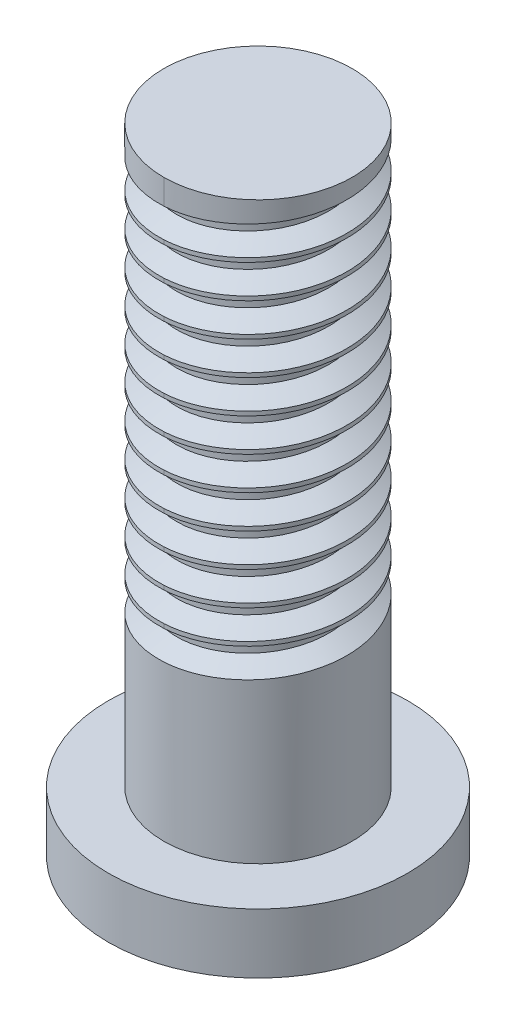
SolidWorks part; units mm, degrees
material "6061-T6 (SS)"
ref_plane "Front Plane" through (0, 0, 0) normal (1, 0, 0) x (0, 1, 0)
ref_plane "Top Plane" through (0, 0, 0) normal (0, 0, 1) x (0, 1, 0)
ref_plane "Right Plane" through (0, 0, 0) normal (0, 1, 0) x (-1, 0, 0)
sketch "Sketch1" plane through (0, 0, 0) normal (1, 0, 0) x (0, 1, 0)
  line L0 (0, 0) -> (-28.8256, 0)
  line L1 (-26.9494, 6.35) -> (-24.4094, 6.35)
  line L2 (-24.4094, 6.35) -> (-24.4094, 4)
  line L3 (-24.4094, 4) -> (0, 4)
  line L5 (0, 4) -> (0, 0)
  line L6 (-17.399, 0) -> (-17.399, 4) construction
  arc A0 (-28.8256, 0) -> (-26.9494, 6.35) centre (-17.1416, 0) cw
  point P7 (-28.4424, 6.35)
  point P11 (-21.0337, 4)
  point P12 (-0.2338, 4)
  point P13 (-17.399, 4)
  point P14 (-27.559, 4)
  dimension "D6" = 11.684
  dimension "D1" = 4
  dimension "D2" = 6.35
  dimension "D5" = 2.54
  dimension "D3" = 7.0104
  dimension "D4" = 17.399
revolve "Revolve1" add sketch "Sketch1" angle 360 about L0 region at (0, -8.6995, 2) region at (0, -23.4299, 2.426)
thread "Thread1" pitch 1.4111 method cut profile "Thread Profile1" start angle 0, offset 0, length 17.399, pitch 1.4111, diameter 8
ref_plane "Plane1" through (-4, 0, 0) normal (0, 0, 1) x (-1, 0, 0)
sketch "Thread Profile1" plane through (-4, 0, 0) normal (0, 0, 1) x (-1, 0, 0)
  line L0 (0, 0) -> (0, 1.4111) construction
  line L11 (0, 0) -> (0, 1.2347)
  line L12 (0, 1.2347) -> (-0.7638, 0.7937)
  line L13 (-0.7638, 0.7937) -> (-0.7638, 0.441)
  line L15 (-0.7638, 0.441) -> (0, 0)
  line L17 (-0.7638, 0.6174) -> (0, 0.6174) construction
  point P2 (0, 0)
  dimension "Pitch" = 1.4111
  dimension "Profile_Angle" = 60
  dimension "Profile_Land" = 0.3528
  dimension "Profile_Height" = 0.7638
equation "\"D1@Sketch1\"=4mm"
equation "\"Wheel Wdith\"= 0.276"
equation "\"wall thickness\"= 0.225"
equation "\"nut thickness\"= 0.23"
equation "\"D3@Sketch1\"=\"Wheel Wdith\""
equation "\"D4@Sketch1\"=\"nut thickness\"*2+\"wall thickness\""
